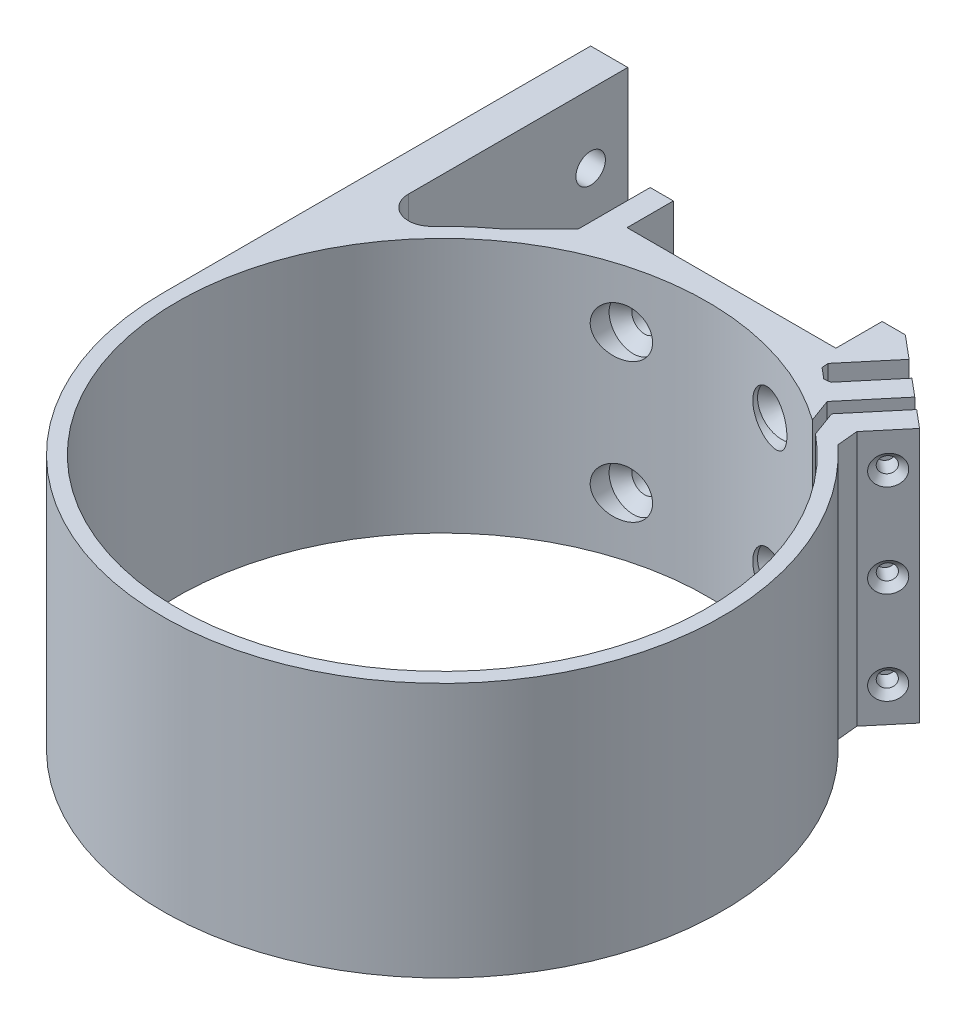
SolidWorks part; units mm, degrees
ref_plane "Front Plane" through (0, 0, 0) normal (0, 0, 1) x (1, 0, 0)
ref_plane "Top Plane" through (0, 0, 0) normal (0, 1, 0) x (1, 0, 0)
ref_plane "Right Plane" through (0, 0, 0) normal (1, 0, 0) x (0, 0, -1)
sketch "Sketch1" plane through (0, 0, 0) normal (0, 1, 0) x (1, 0, 0)
  line L0 (-27.5, 53.6922) -> (-27.5, 72.3012)
  line L5 (-27.5, 72.3012) -> (-22.5, 72.3012)
  line L6 (-22.5, 72.3012) -> (-22.5, 62.325)
  line L7 (-22.5, 62.325) -> (22.5, 62.325)
  line L8 (22.5, 62.325) -> (22.5, 72.3012)
  line L9 (22.5, 72.3012) -> (27.5, 72.3012)
  line L10 (27.5, 72.3012) -> (27.5, 53.6922) construction
  line L11 (31.5122, 51.4401) -> (33.3405, 46.4169)
  line L12 (34.3018, 49.6235) -> (36.2961, 44.1443)
  line L14 (31.5122, 51.4401) -> (40.1266, 61.7062)
  line L15 (34.3018, 49.6235) -> (42.658, 59.5821)
  line L16 (42.658, 59.5821) -> (46.4882, 56.3682)
  line L17 (46.4882, 56.3682) -> (38.2986, 46.6082)
  line L18 (40.1266, 61.7062) -> (36.2963, 64.9202)
  line L19 (36.2963, 64.9202) -> (27.682, 54.654)
  line L20 (27.682, 54.654) -> (23.8518, 57.868)
  line L21 (23.8518, 57.868) -> (32.4661, 68.1341)
  line L22 (32.4661, 68.1341) -> (27.5, 72.3012)
  line L23 (-60.325, 0) -> (-60.325, 92.3012)
  line L24 (-60.325, 92.3012) -> (-52.325, 92.3012)
  line L25 (-52.325, 92.3012) -> (-52.325, 30.02)
  arc A0 (-27.5, 53.6922) -> (-52.325, 30.02) centre (0, 0) ccw
  arc A1 (33.3405, 46.4169) -> (36.2961, 44.1443) centre (0, 0) ccw
  arc A2 (31.5122, 51.4401) -> (27.5, 53.6922) centre (0, 0) ccw construction
  arc A3 (38.2986, 46.6082) -> (34.3018, 49.6235) centre (0, 0) ccw construction
  arc A4 (-60.325, 0) -> (38.2986, 46.6082) centre (0, 0) ccw
  point P9 (0, 62.325)
  point P13 (0, 60.325)
  dimension "D1" = 114.3
  dimension "D2" = 3.175
  dimension "D3" = 45
  dimension "D4" = 5
  dimension "D5" = 5
  dimension "D6" = 2
  dimension "D7" = 20
  dimension "D8" = 2
  dimension "D9" = 3
  dimension "D10" = 120
  dimension "D11" = 13
  dimension "D12" = 5
  dimension "D13" = 5
  dimension "D14" = 8
  dimension "D15" = 20
extrude "Boss-Extrude1" add sketch "Sketch1" along normal mid plane 55
sketch "Sketch4" plane through (0, -27.5, 0) normal (0, -1, 0) x (1, 0, 0)
  line L1 (-22.5, -62.325) -> (22.5, -62.325)
  line L2 (-22.5, -62.325) -> (-22.5, -72.3012)
  line L3 (-22.5, -72.3012) -> (22.5, -72.3012)
  line L4 (22.5, -62.325) -> (22.5, -72.3012)
extrude "Boss-Extrude2" add sketch "Sketch4" against normal blind 4.5
ref_plane "Plane1" through (0, 0, -57.15) normal (0, 0, 1) x (1, 0, 0)
sketch "Sketch6" plane through (0, 0, -57.15) normal (0, 0, 1) x (1, 0, 0)
  line L1 (16, -15) -> (-16, -15) construction
  line L2 (16, -15) -> (16, 15) construction
  line L3 (16, 15) -> (-16, 15) construction
  line L4 (-16, -15) -> (-16, 15) construction
  line L5 (16, -15) -> (-16, 15) construction
  line L6 (16, 15) -> (-16, -15) construction
  point P0 (0, 0)
  dimension "D1" = 32
  dimension "D2" = 30
hole_wizard "CSK for M5 Flat Head Machine Screw1" positions "Sketch10" profile "Sketch12" countersink size "M5" standard "ANSI Metric" end condition through all
sketch "Sketch10" plane through (0, 0, -57.15) normal (0, 0, 1) x (1, 0, 0)
  point P0 (-16, 15)
  point P3 (16, 15)
  point P6 (16, -15)
  point P9 (-16, -15)
sketch "Sketch12" plane through (-16, 15, -57.15) normal (1, 0, 0) x (0, -1, 0)
  line L0 (0, 0) -> (0, 35.1512)
  line L1 (0, 35.1512) -> (2.75, 35.1512)
  line L2 (2.75, 35.1512) -> (2.75, 2.45)
  line L3 (2.75, 2.45) -> (5.2, 0)
  line L5 (5.2, 0) -> (0, 0)
  line L6 (-2.75, 2.45) -> (-5.2, 0) construction
  line L11 (0, -6.35) -> (0, 107.95) construction
  dimension "Thru Hole Dia." = 5.5
  dimension "Thru Hole Depth" = 35.1512
  dimension "Near C'Sink Dia." = 10.4
  dimension "Near C'Sink Angle" = 90
sketch "Sketch13" plane through (0, 0, -57.15) normal (0, 0, 1) x (1, 0, 0)
  circle A0 centre (-16, -15) radius 5.2 construction
  circle A1 centre (16, -15) radius 5.2 construction
  circle A2 centre (16, 15) radius 5.2 construction
  circle A3 centre (-16, 15) radius 5.2 construction
  circle A4 centre (-16, -15) radius 5.2
  circle A5 centre (16, -15) radius 5.2
  circle A6 centre (16, 15) radius 5.2
  circle A7 centre (-16, 15) radius 5.2
extrude "Cut-Extrude1" cut sketch "Sketch13" along normal up to next
chamfer "Chamfer1" distance 3.175 angle 45 2 edges at (-27.5, 0, -53.6922) (38.2986, 0, -46.6082) first distance on face at (-27.5, 0, -62.9967) first distance on face at (7.3811, 0, 15.6185)
chamfer "Chamfer2" distance 1 angle 45 2 edges at (23.8518, 0, -57.868) (27.682, 0, -54.654)
hole_wizard "CSK for M3 Flat Head Machine Screw1" positions "Sketch2" profile "Sketch3" countersink size "M3" standard "ANSI Metric"
sketch "Sketch2" plane through (-0.4755, 0, -0.399) normal (0.766, 0, 0.6428) x (0.6428, 0, -0.766)
  line L0 (63.4646, 27.5) -> (73.0626, 27.5) construction
  point P0 (68.2636, 20)
  point P2 (68.2636, 0)
  point P4 (68.2636, -20)
  point P16 (68.2636, 27.5)
  dimension "D1" = 20
  dimension "D2" = 20
sketch "Sketch3" plane through (43.4035, 20, -52.6919) normal (0, 1, 0) x (0.6428, 0, -0.766)
  line L0 (0, 0) -> (0, 16.0215)
  line L1 (0, 16.0215) -> (1.7, 15)
  line L2 (1.7, 15) -> (1.7, 1.45)
  line L3 (1.7, 1.45) -> (3.15, 0)
  line L5 (3.15, 0) -> (0, 0)
  line L6 (-1.7, 1.45) -> (-3.15, 0) construction
  line L10 (0, 16.0215) -> (-1.7, 15) construction
  line L11 (0, -6.35) -> (0, 107.95) construction
  dimension "Hole Dia." = 3.4
  dimension "Hole Depth" = 15
  dimension "Near C'Sink Dia." = 6.3
  dimension "Near C'Sink Angle" = 90
  dimension "Drill Angle" = 118
fillet "Fillet2" radius 5 1 edges at (-52.325, 0, -30.02)
sketch "Sketch14" plane through (-52.325, 0, 0) normal (1, 0, 0) x (0, 0, -1)
  line L0 (84.3012, 12.7) -> (84.3012, -12.7) construction
  line L1 (84.3012, 12.7) -> (84.3012, 27.5) construction
  line L2 (84.3012, -12.7) -> (84.3012, -27.5) construction
  line L3 (45.03, -27.5) -> (92.3012, -27.5) construction
  line L4 (45.03, 27.5) -> (92.3012, 27.5) construction
  line L5 (92.3012, 27.5) -> (92.3012, -27.5) construction
  arc A0 (84.3012, 38.1) -> (84.3012, -38.1) centre (84.3012, 0) ccw construction
  circle A1 centre (84.3012, 12.7) radius 3.175
  circle A2 centre (84.3012, -12.7) radius 3.175
  dimension "D1" = 38.1
  dimension "D4" = 6.35
  dimension "D2" = 25.4
  dimension "D3" = 8
extrude "Cut-Extrude2" cut sketch "Sketch14" against normal blind 10
